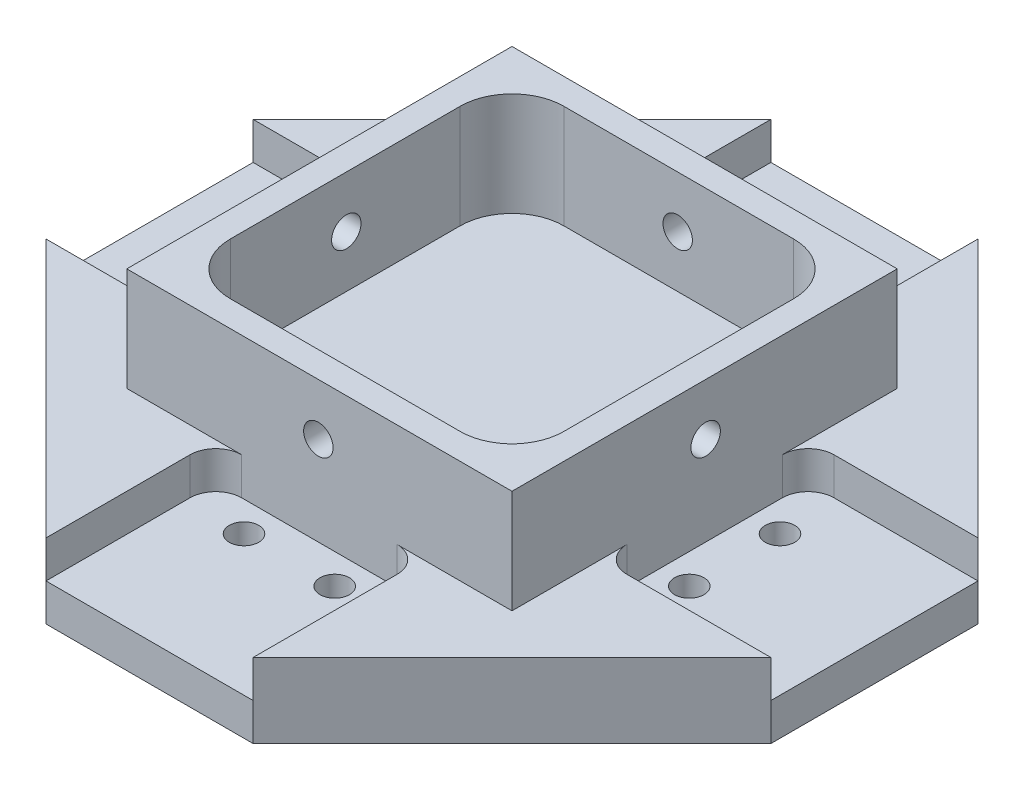
SolidWorks part; units mm, degrees
material "6061 Alloy"
ref_plane "Front Plane" through (0, 0, 0) normal (0, 0, 1) x (1, 0, 0)
ref_plane "Top Plane" through (0, 0, 0) normal (0, 1, 0) x (1, 0, 0)
ref_plane "Right Plane" through (0, 0, 0) normal (1, 0, 0) x (0, 0, -1)
sketch "Sketch1" plane through (0, 0, 0) normal (0, 1, 0) x (1, 0, 0)
  line L1 (0, 0) -> (88.9, 0)
  line L2 (0, 0) -> (0, 88.9)
  line L3 (0, 88.9) -> (88.9, 88.9)
  line L4 (88.9, 0) -> (88.9, 88.9)
  dimension "D1" = 88.9
  dimension "D2" = 88.9
extrude "Boss-Extrude1" add sketch "Sketch1" along normal blind 9.144
sketch "Sketch2" plane through (0, 9.144, 0) normal (0, 1, 0) x (1, 0, 0)
  line L0 (88.9, 88.9) -> (0, 88.9) construction
  line L1 (31.75, 88.9) -> (57.15, 88.9)
  line L2 (31.75, 88.9) -> (31.75, 67.31)
  line L3 (31.75, 67.31) -> (57.15, 67.31)
  line L4 (57.15, 88.9) -> (57.15, 67.31)
  line L5 (0, 88.9) -> (0, 0) construction
  line L6 (0, 57.15) -> (21.59, 57.15)
  line L7 (0, 57.15) -> (0, 31.75)
  line L8 (0, 31.75) -> (21.59, 31.75)
  line L9 (21.59, 57.15) -> (21.59, 31.75)
  line L10 (0, 0) -> (88.9, 0) construction
  line L11 (31.75, 0) -> (57.15, 0)
  line L12 (31.75, 0) -> (31.75, 21.59)
  line L13 (31.75, 21.59) -> (57.15, 21.59)
  line L14 (57.15, 0) -> (57.15, 21.59)
  line L15 (88.9, 0) -> (88.9, 88.9) construction
  line L16 (88.9, 57.15) -> (67.31, 57.15)
  line L17 (88.9, 57.15) -> (88.9, 31.75)
  line L18 (88.9, 31.75) -> (67.31, 31.75)
  line L19 (67.31, 57.15) -> (67.31, 31.75)
  dimension "D1" = 31.75
  dimension "D2" = 25.4
  dimension "D3" = 25.4
  dimension "D4" = 31.75
  dimension "D5" = 25.4
  dimension "D6" = 31.75
  dimension "D7" = 25.4
  dimension "D8" = 31.75
  dimension "D9" = 21.59
  dimension "D10" = 21.59
  dimension "D11" = 21.59
  dimension "D12" = 21.59
extrude "Cut-Extrude1" cut sketch "Sketch2" against normal blind 4.572
sketch "Sketch3" plane through (0, 9.144, 0) normal (0, 1, 0) x (1, 0, 0)
  line L0 (31.75, 88.9) -> (0, 88.9) construction
  line L1 (20.6375, 68.2625) -> (68.2625, 68.2625)
  line L2 (20.6375, 68.2625) -> (20.6375, 20.6375)
  line L3 (20.6375, 20.6375) -> (68.2625, 20.6375)
  line L4 (68.2625, 68.2625) -> (68.2625, 20.6375)
  line L5 (0, 31.75) -> (0, 0) construction
  line L6 (88.9, 31.75) -> (88.9, 57.15) construction
  line L7 (57.15, 88.9) -> (31.75, 88.9) construction
  line L8 (0, 57.15) -> (0, 31.75) construction
  line L9 (31.75, 0) -> (57.15, 0) construction
  circle A0 centre (28.194, 44.45) radius 2.4
  circle A1 centre (44.45, 60.706) radius 2.4
  circle A2 centre (60.706, 44.45) radius 2.4
  circle A3 centre (44.45, 28.194) radius 2.4
  dimension "D5" = 4.8
  dimension "D6" = 4.8
  dimension "D7" = 4.8
  dimension "D8" = 4.8
  dimension "D1" = 47.625
  dimension "D2" = 47.625
  dimension "D3" = 20.6375
  dimension "D4" = 20.6375
  dimension "D9" = 28.194
  dimension "D10" = 28.194
  dimension "D11" = 28.194
  dimension "D12" = 28.194
  dimension "D13" = 23.8125
  dimension "D14" = 23.8125
  dimension "D15" = 23.8125
  dimension "D16" = 23.8125
extrude "Cut-Extrude2" [suppressed] cut sketch "Sketch3" against normal through all contours A2 | A1 | A0 | A3
sketch "Sketch4" plane through (0, 4.572, 0) normal (0, 1, 0) x (1, 0, 0)
  line L0 (0, 57.15) -> (0, 31.75) construction
  line L1 (57.15, 88.9) -> (31.75, 88.9) construction
  line L2 (88.9, 31.75) -> (88.9, 57.15) construction
  line L3 (31.75, 0) -> (57.15, 0) construction
  line L4 (0, 31.75) -> (21.59, 31.75) construction
  line L5 (31.75, 21.59) -> (31.75, 0) construction
  line L6 (67.31, 31.75) -> (88.9, 31.75) construction
  line L7 (57.15, 67.31) -> (57.15, 88.9) construction
  circle A0 centre (71.755, 50.0126) radius 1.8034
  circle A1 centre (71.755, 38.8874) radius 1.8034
  circle A2 centre (50.0126, 71.755) radius 1.8034
  circle A3 centre (38.8874, 71.755) radius 1.8034
  circle A4 centre (17.145, 50.0126) radius 1.8034
  circle A5 centre (17.145, 38.8874) radius 1.8034
  circle A6 centre (38.8874, 17.145) radius 1.8034
  circle A7 centre (50.0126, 17.145) radius 1.8034
  dimension "D1" = 3.6068
  dimension "D2" = 3.6068
  dimension "D3" = 3.6068
  dimension "D4" = 3.6068
  dimension "D5" = 3.6068
  dimension "D6" = 3.6068
  dimension "D7" = 3.6068
  dimension "D8" = 3.6068
  dimension "D9" = 17.145
  dimension "D10" = 17.145
  dimension "D11" = 17.145
  dimension "D12" = 17.145
  dimension "D13" = 17.145
  dimension "D14" = 17.145
  dimension ".313" = 17.145
  dimension "D16" = 17.145
  dimension "D17" = 11.1252
  dimension "D18" = 7.1374
  dimension "D19" = 7.1374
  dimension "D20" = 11.1252
  dimension "D21" = 7.1374
  dimension "D22" = 11.1252
  dimension "D23" = 7.1374
  dimension "D24" = 11.1252
extrude "Cut-Extrude3" cut sketch "Sketch4" against normal through all
sketch "Sketch5" plane through (0, 9.144, 0) normal (0, 1, 0) x (1, 0, 0)
  line L0 (88.9, 88.9) -> (57.15, 88.9) construction
  line L1 (88.9, 31.75) -> (88.9, 57.15) construction
  circle A0 centre (44.45, 44.45) radius 6.35
  dimension "D1" = 12.7
  dimension "D2" = 44.45
  dimension "D3" = 44.45
extrude "Cut-Extrude4" [suppressed] cut sketch "Sketch5" against normal through all
sketch "Sketch6" plane through (0, 9.144, 0) normal (0, 1, 0) x (1, 0, 0)
  line L0 (88.9, 31.75) -> (57.15, 0)
  line L1 (57.15, 0) -> (88.9, 0)
  line L2 (88.9, 0) -> (88.9, 31.75)
extrude "Cut-Extrude5" cut sketch "Sketch6" against normal through all
sketch "Sketch7" plane through (0, 9.144, 0) normal (0, 1, 0) x (1, 0, 0)
  line L0 (0, 88.9) -> (0, 57.15) construction
  line L1 (20.828, 68.072) -> (68.072, 68.072)
  line L2 (20.828, 68.072) -> (20.828, 20.828)
  line L3 (20.828, 20.828) -> (68.072, 20.828)
  line L4 (68.072, 68.072) -> (68.072, 20.828)
  line L5 (0, 0) -> (31.75, 0) construction
  line L7 (24.003, 24.003) -> (64.897, 24.003)
  line L8 (24.003, 24.003) -> (24.003, 64.897)
  line L9 (24.003, 64.897) -> (64.897, 64.897)
  line L10 (64.897, 24.003) -> (64.897, 64.897)
  dimension "D1" = 47.244
  dimension "D2" = 47.244
  dimension "D3" = 20.828
  dimension "D4" = 20.828
  dimension "D5" = 3.175
  dimension "D6" = 3.175
  dimension "D7" = 3.175
  dimension "D8" = 3.175
extrude "Boss-Extrude2" add sketch "Sketch7" along normal blind 12.7 and the other way up to next (4.572 mm away)
fillet "Fillet9" radius 6.35 1 edges at (64.897, 15.494, -24.003)
fillet "Fillet10" radius 6.35 1 edges at (24.003, 15.494, -24.003)
fillet "Fillet11" radius 6.35 1 edges at (64.897, 15.494, -64.897)
fillet "Fillet12" radius 6.35 1 edges at (24.003, 15.494, -64.897)
fillet "Fillet15" radius 3.175 1 edges at (20.828, 6.858, -57.15)
fillet "Fillet16" radius 3.175 1 edges at (31.75, 6.858, -20.828)
fillet "Fillet17" radius 3.175 1 edges at (57.15, 6.858, -20.828)
fillet "Fillet18" radius 3.175 1 edges at (68.072, 6.858, -57.15)
fillet "Fillet19" radius 3.175 1 edges at (68.072, 6.858, -31.75)
fillet "Fillet20" radius 3.175 1 edges at (31.75, 6.858, -68.072)
fillet "Fillet21" radius 3.175 1 edges at (57.15, 6.858, -68.072)
fillet "Fillet22" radius 3.175 1 edges at (20.828, 6.858, -31.75)
sketch "Sketch9" plane through (0, 0, -68.072) normal (0, 0, -1) x (-1, 0, 0)
  line L0 (-68.072, 21.844) -> (-68.072, 9.144) construction
  line L1 (-68.072, 21.844) -> (-20.828, 21.844) construction
  circle A0 centre (-44.323, 15.494) radius 1.8034
  dimension "D1" = 3.6068
  dimension "D2" = 23.749
  dimension "D3" = 6.35
extrude "Cut-Extrude6" cut sketch "Sketch9" against normal through all
sketch "Sketch10" plane through (68.072, 0, 0) normal (1, 0, 0) x (0, 0, -1)
  line L0 (20.828, 21.844) -> (68.072, 21.844) construction
  line L1 (20.828, 21.844) -> (20.828, 9.144) construction
  circle A0 centre (44.577, 15.494) radius 1.8034
  dimension "D1" = 3.6068
  dimension "D2" = 6.35
  dimension "D3" = 23.749
extrude "Cut-Extrude7" cut sketch "Sketch10" against normal through all
sketch "Sketch12" plane through (0, 9.144, 0) normal (0, 1, 0) x (1, 0, 0)
  line L0 (0, 31.75) -> (31.75, 0)
  line L1 (31.75, 0) -> (0, 0)
  line L2 (0, 0) -> (0, 31.75)
  line L3 (57.15, 88.9) -> (88.9, 57.15)
  line L4 (88.9, 57.15) -> (88.9, 88.9)
  line L5 (88.9, 88.9) -> (57.15, 88.9)
  line L6 (0, 57.15) -> (31.75, 88.9)
  line L7 (31.75, 88.9) -> (0, 88.9)
  line L8 (0, 88.9) -> (0, 57.15)
sketch "Sketch14" plane through (0, 0, 0) normal (0, -1, 0) x (1, 0, 0)
  line L0 (60.2924, -60.2924) -> (28.8616, -28.8616) construction
  line L6 (24.003, -58.547) -> (24.003, -30.353) construction
  line L7 (30.353, -24.003) -> (58.547, -24.003) construction
  circle A0 centre (28.8616, -28.8616) radius 2.5797
  circle A1 centre (60.2924, -60.2924) radius 2.5797
  point P0 (44.577, -44.577)
  dimension "D1" = 44.45
  dimension "D2" = 5.1594
  dimension "D3" = 5.1594
  dimension "D4" = 20.574
  dimension "D5" = 20.574
extrude "Cut-Extrude9" cut sketch "Sketch14" against normal through all
extrude "Cut-Extrude10" cut sketch "Sketch12" against normal through all
equation "\"hinge_hole\"= 0.142in"
equation "\"D1@Sketch4\"=\"hinge_hole\""
equation "\"D2@Sketch4\"=\"hinge_hole\""
equation "\"D3@Sketch4\"=\"hinge_hole\""
equation "\"D4@Sketch4\"=\"hinge_hole\""
equation "\"D5@Sketch4\"=\"hinge_hole\""
equation "\"D6@Sketch4\"=\"hinge_hole\""
equation "\"D7@Sketch4\"=\"hinge_hole\""
equation "\"D8@Sketch4\"=\"hinge_hole\""
equation "\"hinge_hole_dist\"= 0.297 + 0.25"
equation "\".313@Sketch4\"=.675"
equation "\"hinge_hole_sep\"=0.438"
equation "\"hinge_hole_from_wall\"= ( 1 - \"hinge_hole_sep\" ) / 2"
equation "\"D17@Sketch4\"=\"hinge_hole_sep\""
equation "\"D18@Sketch4\"=\"hinge_hole_from_wall\""
equation "\"D19@Sketch4\"=\"hinge_hole_from_wall\""
equation "\"D20@Sketch4\"=\"hinge_hole_sep\""
equation "\"D21@Sketch4\"=\"hinge_hole_from_wall\""
equation "\"D22@Sketch4\"=\"hinge_hole_sep\""
equation "\"D23@Sketch4\"=\"hinge_hole_from_wall\""
equation "\"D24@Sketch4\"=\"hinge_hole_sep\""
equation "\"D9@Sketch2\"=\"hinge_hole_dist\" + (0.6-0.297)"
equation "\"D12@Sketch2\"=\"hinge_hole_dist\" + (0.6-0.297)"
equation "\"D11@Sketch2\"=\"hinge_hole_dist\" + (0.6-0.297)"
equation "\"D10@Sketch2\"=\"hinge_hole_dist\" + (0.6-0.297)"
